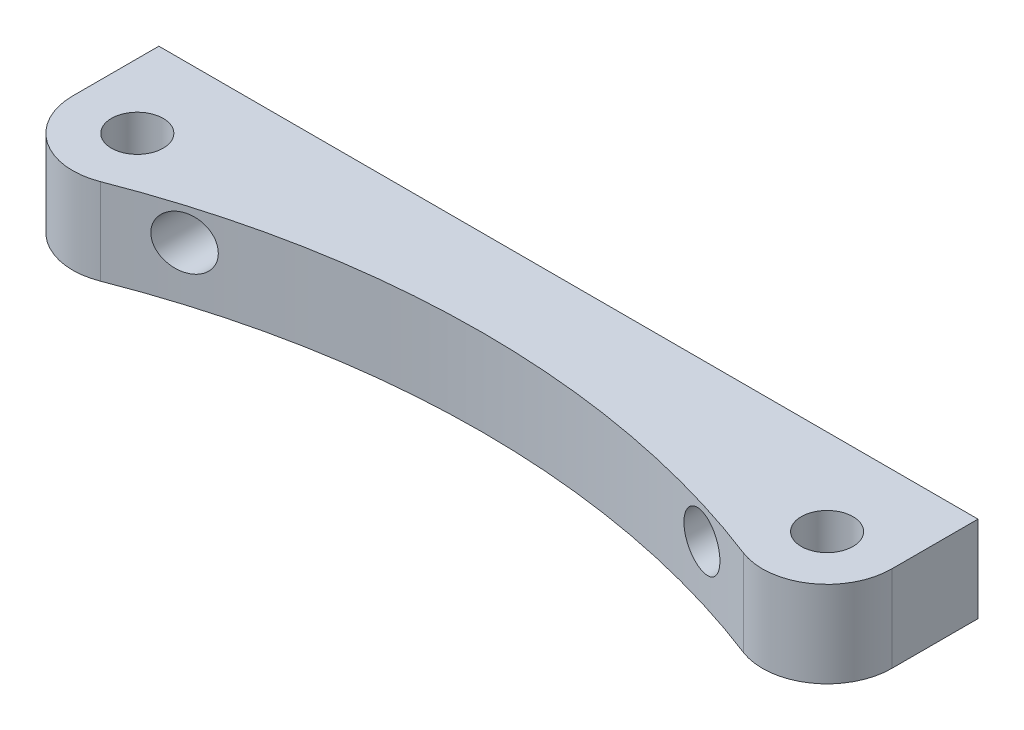
SolidWorks part; units mm, degrees
ref_plane "Front Plane" through (0, 0, 0) normal (0, 0, 1) x (1, 0, 0)
ref_plane "Top Plane" through (0, 0, 0) normal (0, 1, 0) x (1, 0, 0)
ref_plane "Right Plane" through (0, 0, 0) normal (1, 0, 0) x (0, 0, -1)
sketch "Sketch1" plane through (0, 0, 0) normal (0, 1, 0) x (1, 0, 0)
  line L0 (0, 0) -> (50.8, 0) construction
  line L4 (-4.7625, 6.35) -> (-4.7625, 0)
  line L5 (55.5625, 0) -> (55.5625, 6.35)
  line L7 (-4.7625, 6.35) -> (55.5625, 6.35)
  arc A0 (-4.7625, 0) -> (1.7253, -4.439) centre (0, 0) ccw
  arc A1 (49.0747, -4.439) -> (55.5625, 0) centre (50.8, 0) ccw
  circle A2 centre (0, 0) radius 1.905
  circle A3 centre (50.8, 0) radius 1.905
  arc A4 (1.7253, -4.439) -> (49.0747, -4.439) centre (25.4, -65.3521) cw
  point P3 (25.4, 0)
  dimension "D3" = 3.81
  dimension "D4" = 4.7625
  dimension "D1" = 6.35
  dimension "D2" = 50.8
  dimension "D5" = 6.35
extrude "Boss-Extrude1" add sketch "Sketch1" along normal blind 6.35
sketch "Sketch2" plane through (0, 0, -6.35) normal (0, 0, -1) x (-1, 0, 0)
  circle A4 centre (-6.35, 3.9688) radius 1.905
  circle A5 centre (-44.45, 3.9688) radius 1.905
  point P4 (0, 0)
  point P5 (0, 0)
  point P6 (-3.218, 3.7541)
  point P7 (-6.2361, 6.0865)
  point P8 (-6.35, 3.9688)
  point P9 (-44.45, 3.9688)
  point P14 (-6.35, 3.9688)
  point P15 (-6.35, 3.9688)
  dimension "D1" = 3.81
extrude "Cut-Extrude1" cut sketch "Sketch2" against normal up to next
